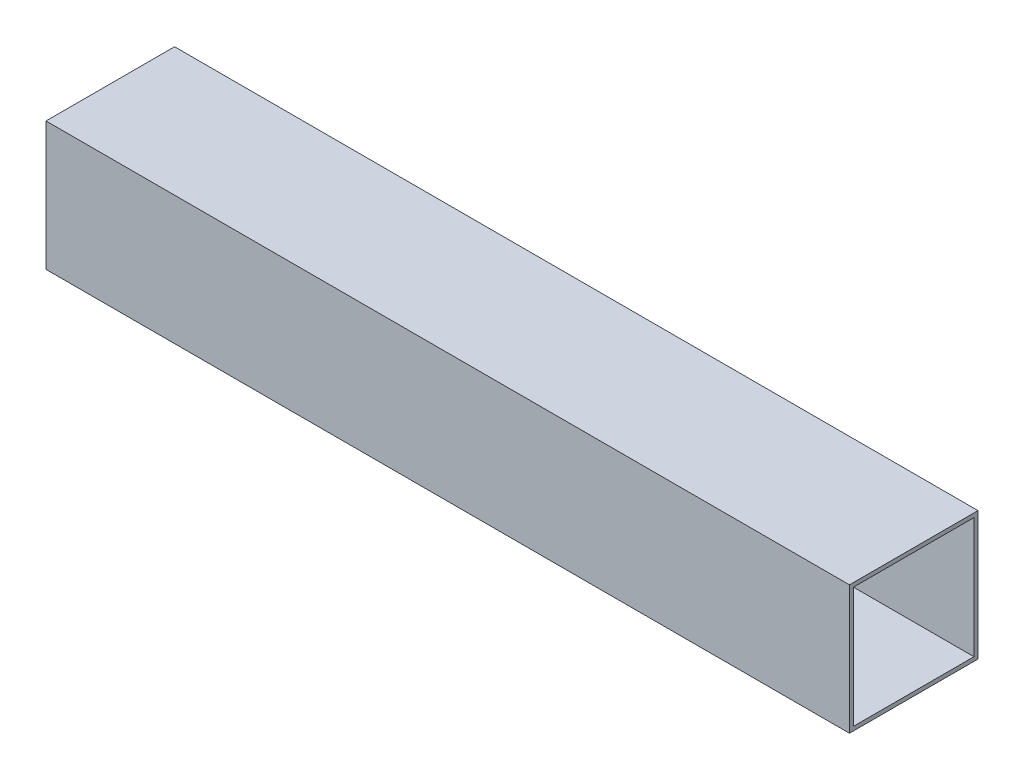
SolidWorks part; units mm, degrees
ref_plane "Front Plane" through (0, 0, 0) normal (0, 0, 1) x (1, 0, 0)
ref_plane "Top Plane" through (0, 0, 0) normal (0, 1, 0) x (1, 0, 0)
ref_plane "Right Plane" through (0, 0, 0) normal (1, 0, 0) x (0, 0, -1)
sketch "Sketch1" plane through (0, 0, 0) normal (1, 0, 0) x (0, 0, -1)
  line L0 (-98.425, 3.175) -> (-98.425, 98.425)
  line L1 (0, 0) -> (-101.6, 0)
  line L2 (0, 0) -> (0, 101.6)
  line L3 (0, 101.6) -> (-101.6, 101.6)
  line L4 (-101.6, 0) -> (-101.6, 101.6)
  line L5 (-3.175, 98.425) -> (-98.425, 98.425)
  line L6 (-3.175, 3.175) -> (-3.175, 98.425)
  line L7 (-3.175, 3.175) -> (-98.425, 3.175)
  dimension "D1" = 101.6
  dimension "D2" = 101.6
  dimension "D3" = 3.175
extrude "Boss-Extrude1" add sketch "Sketch1" along normal blind 635
